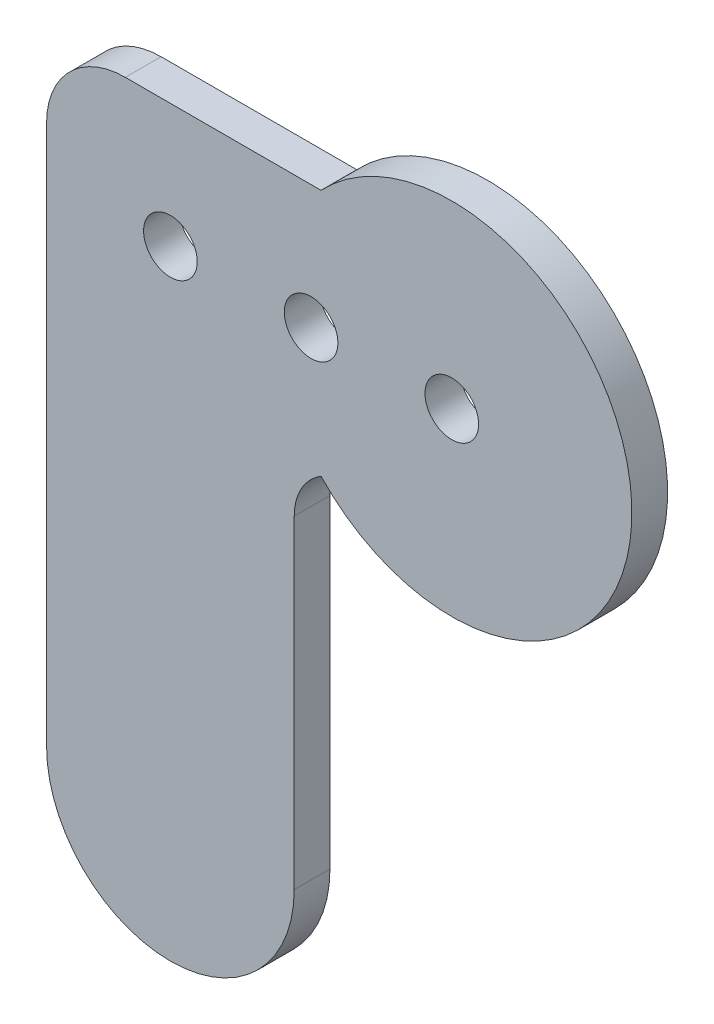
SolidWorks part; units mm, degrees
ref_plane "Front Plane" through (0, 0, 0) normal (0, 0, 1) x (1, 0, 0)
ref_plane "Top Plane" through (0, 0, 0) normal (0, 1, 0) x (1, 0, 0)
ref_plane "Right Plane" through (0, 0, 0) normal (1, 0, 0) x (0, 0, -1)
sketch "Sketch1" plane through (0, 0, 0) normal (0, 0, 1) x (1, 0, 0)
  line L0 (-11.619, 11) -> (-36, 11)
  line L1 (-36, 11) -> (-36, -44)
  line L2 (-14, -44) -> (-14, -11)
  line L3 (-14, -11) -> (-11.619, -11)
  arc A0 (-11.619, -11) -> (-11.619, 11) centre (0, 0) ccw
  arc A1 (-36, -44) -> (-14, -44) centre (-25, -44) ccw
  dimension "D1" = 32
  dimension "D7" = 25
  dimension "D2" = 11
  dimension "D3" = 11
  dimension "D4" = 44
  dimension "D6" = 22
extrude "Boss-Extrude1" add sketch "Sketch1" along normal blind 3.175
fillet "Fillet1" radius 7 1 edges at (-36, 11, 1.5875)
fillet "Fillet2" radius 5 1 edges at (-14, -11, 1.5875)
sketch "Sketch2" plane through (0, 0, 3.175) normal (0, 0, 1) x (1, 0, 0)
  circle A0 centre (0, 0) radius 2.3813
  dimension "D1" = 4.7625
extrude "Cut-Extrude1" cut sketch "Sketch2" against normal through all
pattern_linear "LPattern1" count 3 spacing 12.5 along (-1, 0, 0) of "Cut-Extrude1"
